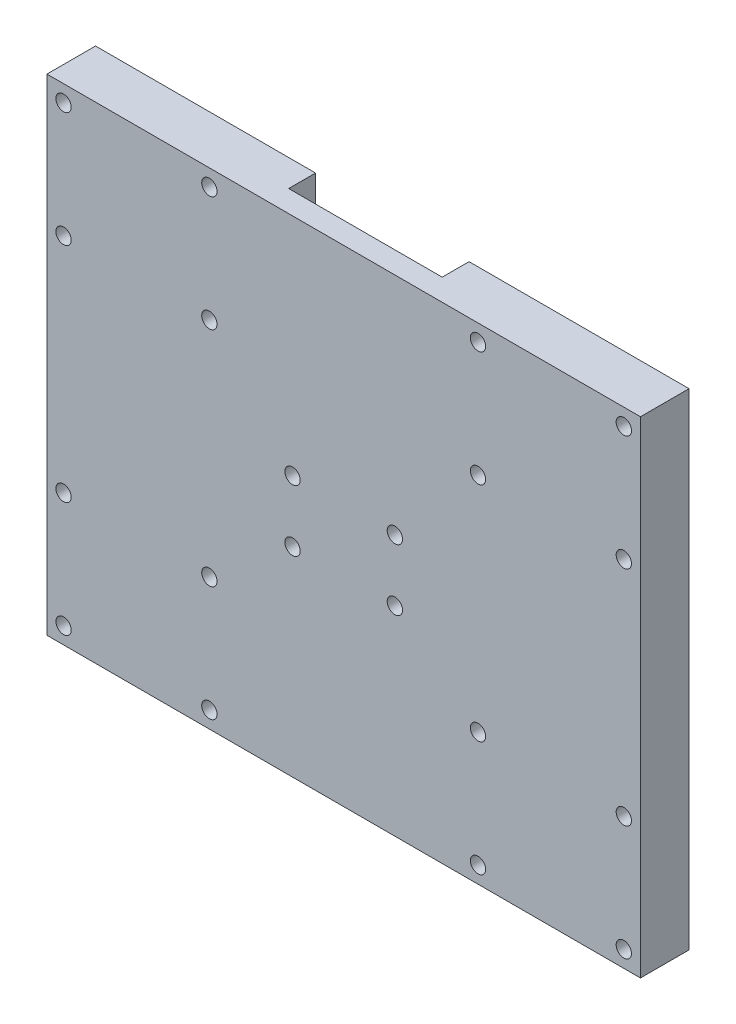
SolidWorks part; units mm, degrees
ref_plane "Piano frontale" through (0, 0, 0) normal (0, 0, 1) x (1, 0, 0)
ref_plane "Piano superiore" through (0, 0, 0) normal (0, 1, 0) x (1, 0, 0)
ref_plane "Piano destro" through (0, 0, 0) normal (1, 0, 0) x (0, 0, -1)
sketch "Schizzo1" plane through (0, 0, 0) normal (0, 0, 1) x (1, 0, 0)
  line L1 (116, -95) -> (-116, -95)
  line L2 (116, -95) -> (116, 95)
  line L3 (116, 95) -> (-116, 95)
  line L4 (-116, -95) -> (-116, 95)
  line L5 (116, -95) -> (-116, 95) construction
  line L6 (116, 95) -> (-116, -95) construction
  point P0 (0, 0)
  dimension "D1" = 232
  dimension "D2" = 190
extrude "Estrusione-Estrusione1" add sketch "Schizzo1" along normal blind 19
sketch "Schizzo3" plane through (0, 0, 19) normal (0, 0, 1) x (1, 0, 0)
  line L0 (20, 7) -> (-20, 7) construction
  line L1 (-20, 7) -> (20, -17) construction
  line L2 (20, -17) -> (20, 7) construction
  line L3 (20, 7) -> (-20, -17) construction
  line L4 (-20, -17) -> (-20, 7) construction
  line L5 (-20, -17) -> (20, -17) construction
  circle A8 centre (20, 7) radius 3
  circle A9 centre (-20, 7) radius 3
  circle A10 centre (-20, -17) radius 3
  circle A11 centre (20, -17) radius 3
  circle A14 centre (-109.5, 88.5) radius 3
  circle A15 centre (-52.5, 88.5) radius 3
  circle A18 centre (-109.5, 43.5) radius 3
  circle A19 centre (-52.5, 43.5) radius 3
  circle A24 centre (-109.5, -88.5) radius 3
  circle A25 centre (-109.5, -43.5) radius 3
  circle A26 centre (-52.5, -88.5) radius 3
  circle A27 centre (-52.5, -43.5) radius 3
  point P21 (0, -5)
  dimension "D1" = 40
  dimension "D2" = 24
extrude "Taglio-Estrusione1" cut sketch "Schizzo3" against normal through all
sketch "Schizzo4" plane through (0, 95, 0) normal (0, 1, 0) x (1, 0, 0)
  line L0 (116, 0) -> (-116, 0) construction
  line L1 (30, 0) -> (-30, 0)
  line L2 (30, 0) -> (30, -10.5)
  line L3 (30, -10.5) -> (-30, -10.5)
  line L4 (-30, 0) -> (-30, -10.5)
  dimension "D1" = 10.5
extrude "Taglio-Estrusione2" cut sketch "Schizzo4" against normal through all
mirror "Specchia1" about plane through (0, 0, 0) normal (1, 0, 0) of "Taglio-Estrusione1"
